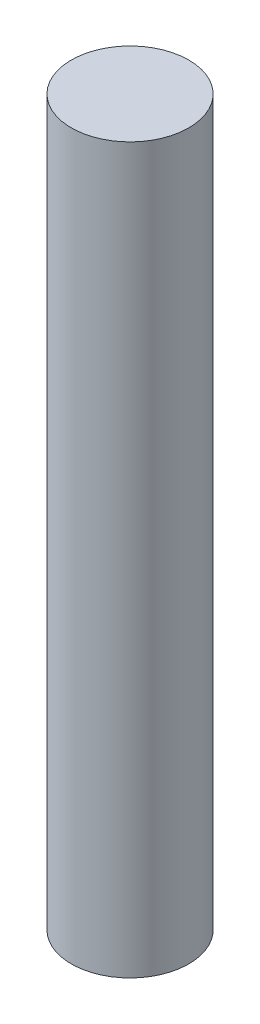
SolidWorks part; units mm, degrees
ref_plane "Alzado" through (0, 0, 0) normal (0, 0, 1) x (1, 0, 0)
ref_plane "Planta" through (0, 0, 0) normal (0, 1, 0) x (1, 0, 0)
ref_plane "Vista lateral" through (0, 0, 0) normal (1, 0, 0) x (0, 0, -1)
sketch "Croquis1" plane through (0, 0, 0) normal (0, 1, 0) x (1, 0, 0)
  circle A0 centre (0, 0) radius 4.7625
  dimension "D1" = 9.525
extrude "Saliente-Extruir1" add sketch "Croquis1" along normal blind 58.68
sketch "Croquis2" plane through (0, 58.68, 0) normal (0, 1, 0) x (1, 0, 0)
  circle A0 centre (0, 0) radius 2
  dimension "D1" = 4
